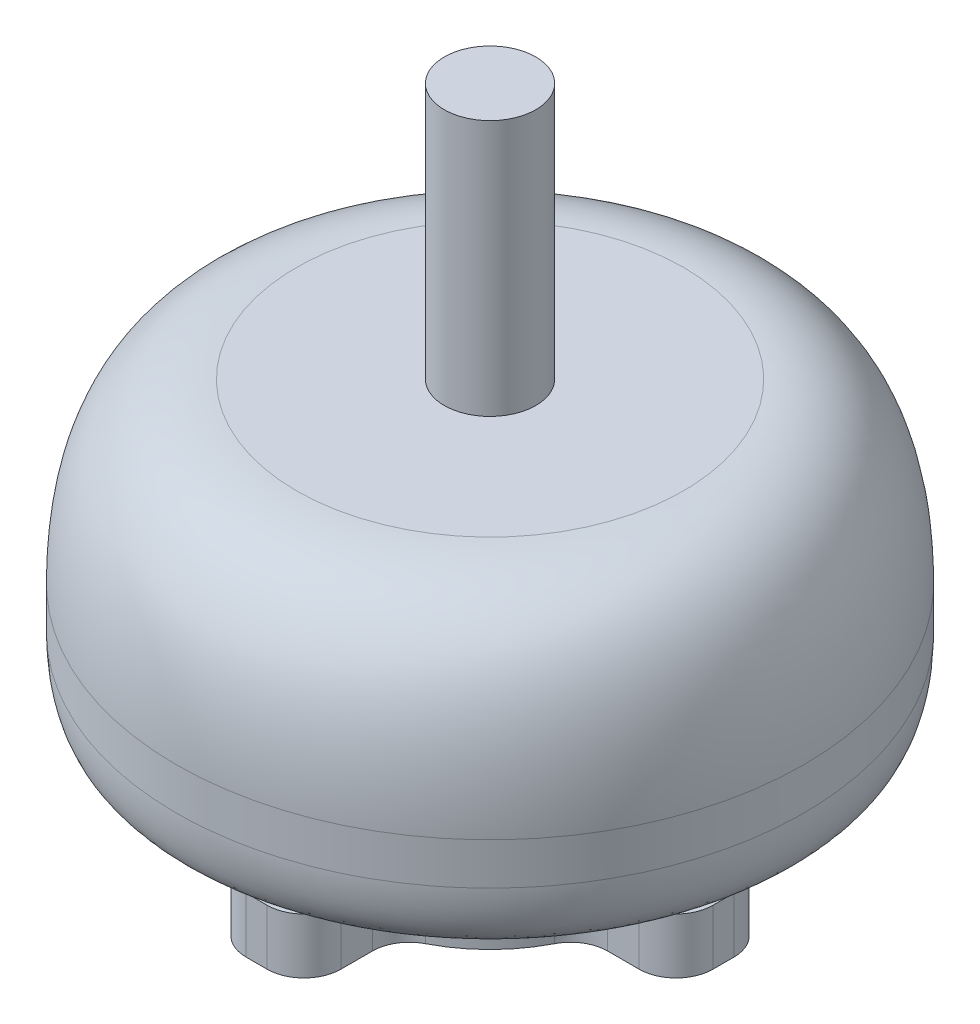
SolidWorks part; units mm, degrees
ref_plane "Front Plane" through (0, 0, 0) normal (0, 0, 1) x (1, 0, 0)
ref_plane "Top Plane" through (0, 0, 0) normal (0, 1, 0) x (1, 0, 0)
ref_plane "Right Plane" through (0, 0, 0) normal (1, 0, 0) x (0, 0, -1)
sketch "Sketch1" plane through (0, 0, 0) normal (0, 1, 0) x (1, 0, 0)
  line L0 (0, 0) -> (0, 12.63) construction
  line L1 (-2.565, 7.6093) -> (-2.565, 12.63)
  line L2 (-2.565, 12.63) -> (2.565, 12.63)
  line L3 (2.565, 12.63) -> (2.565, 7.6093)
  line L4 (0, 8.03) -> (0, 6.26) construction
  circle A0 centre (0, 0) radius 6.26
  circle A1 centre (0, 0) radius 8.03
  circle A2 centre (0, 9.57) radius 1.21
  circle A3 centre (0, 0) radius 7.145
  circle A4 centre (0, 0) radius 16.97
  circle A5 centre (0, 0) radius 2.475
  point P14 (0, 7.145)
  dimension "D1" = 12.52
  dimension "D2" = 16.06
  dimension "D3" = 2.42
  dimension "D4" = 1.85
  dimension "D7" = 33.94
  dimension "D8" = 4.95
  dimension "D5" = 5.13
  dimension "D6" = 8.36
extrude "Boss-Extrude1" add sketch "Sketch1" along normal blind 3 contours A0 A1 | A3 | A0 region at (0, 0, -7.8029)
extrude "Boss-Extrude3" add sketch "Sketch1<4>" along normal blind 3 contours A1 L3 L2 L1 A2 region at (-2.4932, 0, -10.1197)
sketch "Sketch1<4>" plane through (0, 0, 0) normal (0, 1, 0) x (1, 0, 0) same geometry as "Sketch1"
fillet "Fillet1" radius 2 4 edges at (2.565, 1.5, -12.63) (-2.565, 1.5, -12.63) (-2.565, 1.5, -7.6093) (2.565, 1.5, -7.6093)
pattern_circular "CirPattern1" count 4 over 360 about axis through (0, 3, 0) along (0, -1, 0) of "Fillet1", "Boss-Extrude3"
extrude "Boss-Extrude4" add sketch "Sketch1<5>" along normal blind 3.2 from surface contours A3 A0 | A0 A5 | A5 region at (-6.0829, 0, 0) region at (-6.9429, 0, 0) region at (0, 0, 0) starting at face at (0, 3, 0)
sketch "Sketch1<5>" plane through (0, 0, 0) normal (0, 1, 0) x (1, 0, 0) same geometry as "Sketch1"
extrude "Boss-Extrude5" add sketch "Sketch1<6>" along normal blind 14.85 from surface contours A4 starting at face at (0, 6.2, 7.145)
sketch "Sketch1<6>" plane through (0, 0, 0) normal (0, 1, 0) x (1, 0, 0) same geometry as "Sketch1"
extrude "Boss-Extrude6" add sketch "Sketch1<7>" along normal blind 13.86 from surface contours A5 region at (0, 0, 0) starting at face at (0, 21.05, 16.97)
sketch "Sketch1<7>" plane through (0, 0, 0) normal (0, 1, 0) x (1, 0, 0) same geometry as "Sketch1"
sketch "Sketch2" plane through (0, 0, 0) normal (0, 0, 1) x (1, 0, 0)
  line L0 (-16.97, 6.2) -> (16.97, 6.2) construction
  line L1 (16.97, 21.05) -> (-16.97, 21.05) construction
  line L2 (-16.97, 6.2) -> (16.97, 6.2)
  line L3 (16.97, 21.05) -> (-16.97, 21.05)
  line L4 (16.97, 6.2) -> (16.97, 21.05) construction
  line L5 (16.97, 6.2) -> (16.97, 21.05)
  line L6 (15.264, 21.05) -> (10.6654, 21.05) construction
  line L7 (0, 21.05) -> (0, 6.2) construction
  spline S0 degree 3 poles (10.47, 21.05) (18.5455, 21.05) (17.0569, 9.1675) (16.47, 6.2) knots 0 0 0 0 1 1 1 1
  dimension "D1" = 0.5
  dimension "D2" = 6.5
revolve "Cut-Revolve2" cut sketch "Sketch2" angle 360 about L7 region at (15.6549, 19.0967, 0)
fillet "Fillet3" radius 1 1 edges at (0, 6.2, 16.97) second distance 3 first distance on face at (0, 6.2, 7.145)
